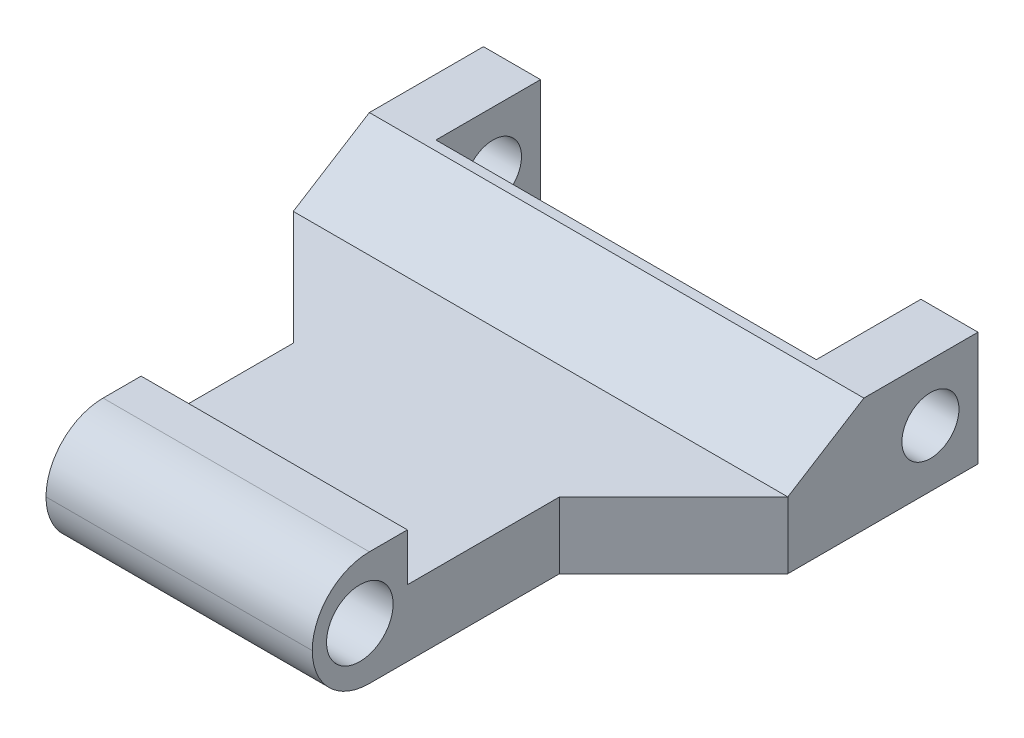
SolidWorks part; units mm, degrees
ref_plane "Plano frontal" through (0, 0, 0) normal (0, 0, 1) x (1, 0, 0)
ref_plane "Plano superior" through (0, 0, 0) normal (0, 1, 0) x (1, 0, 0)
ref_plane "Plano direito" through (0, 0, 0) normal (1, 0, 0) x (0, 0, -1)
sketch "Esboço1" plane through (0, 0, 0) normal (0, 1, 0) x (1, 0, 0)
  line L0 (0, -10.2871) -> (0, 21.2687) construction
  line L1 (7, -10.291) -> (-7, -10.291)
  line L2 (-7, -10.291) -> (-7, 2.709)
  line L3 (-7, 2.709) -> (-13, 8.709)
  line L4 (-13, 8.709) -> (-13, 18.709)
  line L10 (13, 8.709) -> (13, 18.709)
  line L11 (7, 2.709) -> (13, 8.709)
  line L12 (7, -10.291) -> (7, 2.709)
  line L13 (-13, 18.709) -> (13, 18.709)
  point P18 (0, 13.209)
  point P23 (0, -10.291)
  dimension "D1" = 10
  dimension "D2" = 29
  dimension "D3" = 13
  dimension "D4" = 26
  dimension "D6" = 7
extrude "Ressalto-extrusão1" add sketch "Esboço1" along normal blind 6
sketch "Esboço4" plane through (-13, 0, 0) normal (-1, 0, 0) x (0, 0, 1)
  line L9 (-18.709, 6) -> (-18.709, 0) construction
  line L10 (-8.709, 6) -> (-2.709, 6) construction
  line L11 (10.291, 6) -> (10.291, 0) construction
  line L12 (-18.709, 6) -> (-8.709, 6) construction
  line L13 (-12.709, 6) -> (-8.709, 3.5)
  line L14 (-8.709, 3.5) -> (5.291, 3.5)
  line L17 (-12.709, 6) -> (-12.709, 13.3089)
  line L18 (-12.709, 13.3089) -> (5.291, 13.3089)
  line L19 (5.291, 13.3089) -> (5.291, 3.5)
  dimension "D1" = 6
  dimension "D2" = 2.5
  dimension "D3" = 5
extrude "Corte-extrusão1" cut sketch "Esboço4" against normal through all
sketch "Esboço5" plane through (-7, 0, 0) normal (-1, 0, 0) x (0, 0, 1)
  line L0 (8.9942, 3) -> (-21.955, 3) construction
  line L1 (7.791, 7.5701) -> (7.791, -1.4595) construction
  line L2 (5.291, 6) -> (10.291, 6) construction
  circle A0 centre (7.791, 3) radius 1.75
  point P8 (7.791, 6)
  dimension "D1" = 3.5
extrude "Corte-extrusão2" cut sketch "Esboço5" against normal through all
fillet "Filete1" radius 3 2 edges at (0, 0, 10.291) (0, 6, 10.291)
sketch "Esboço6" plane through (0, 6, 0) normal (0, 1, 0) x (1, 0, 0)
  line L0 (0, 21.2181) -> (0, -13.3224) construction
  line L1 (-10, 18.709) -> (-10, 13.209)
  line L2 (13, 18.709) -> (-13, 18.709) construction
  line L3 (-10, 13.209) -> (10, 13.209)
  line L4 (-10, 18.709) -> (10, 18.709)
  line L5 (-13, 18.709) -> (-13, 12.709) construction
  line L6 (10, 18.709) -> (10, 13.209)
  point P12 (0, 13.209)
  point P13 (0, 18.709)
  dimension "D1" = 5.5
  dimension "D2" = 3
extrude "Corte-extrusão3" cut sketch "Esboço6" against normal through all
sketch "Esboço7" plane through (-13, 0, 0) normal (-1, 0, 0) x (0, 0, 1)
  line L0 (-21.4424, 3) -> (-2.4938, 3) construction
  line L1 (-18.709, 6) -> (-18.709, 0) construction
  circle A0 centre (-16.209, 3) radius 1.5
  dimension "D1" = 3
  dimension "D2" = 2.5
extrude "Corte-extrusão4" cut sketch "Esboço7" against normal through all
